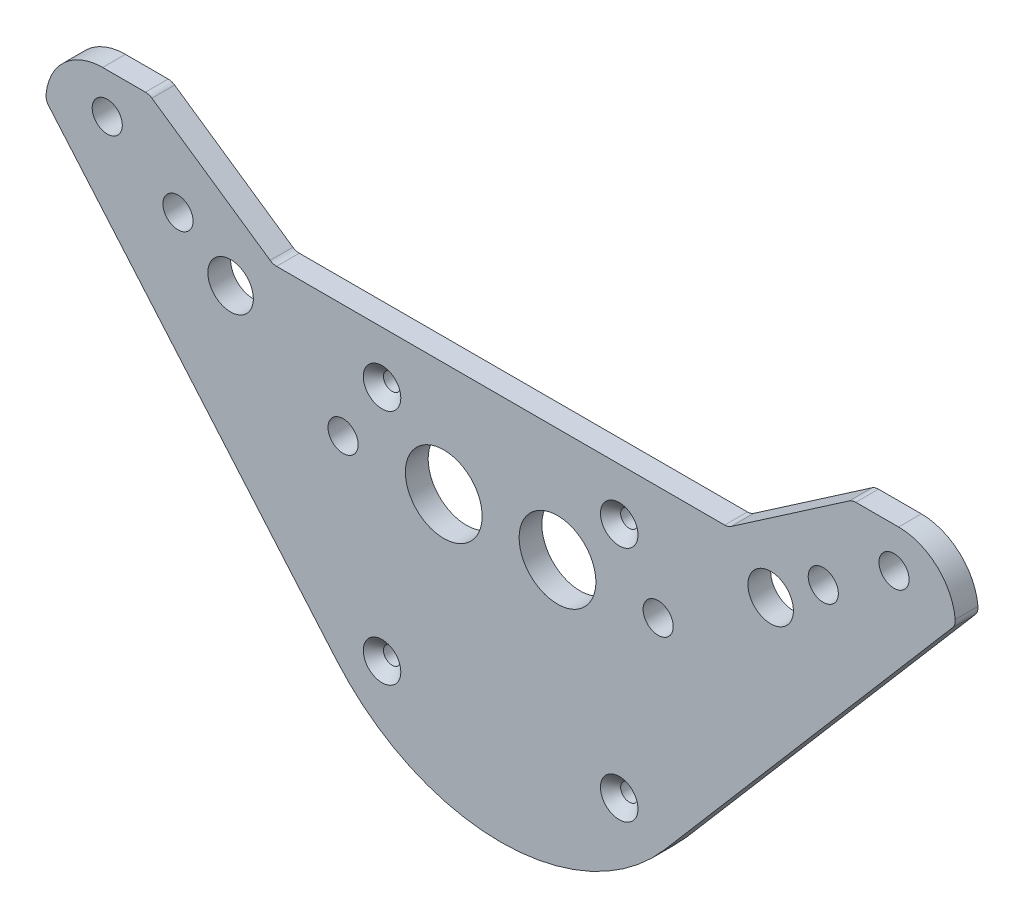
SolidWorks part; units mm, degrees
material "Thornel Mat VMA"
ref_plane "前视基准面" through (0, 0, 0) normal (0, 0, 1) x (1, 0, 0)
ref_plane "上视基准面" through (0, 0, 0) normal (0, 1, 0) x (1, 0, 0)
ref_plane "右视基准面" through (0, 0, 0) normal (1, 0, 0) x (0, 0, -1)
other "Configuration Table"
sketch "草图1" plane through (0, 0, 0) normal (0, 0, 1) x (1, 0, 0)
  line L1 (-80, -60) -> (80, -60)
  line L2 (-80, -60) -> (-80, 60)
  line L3 (-80, 60) -> (80, 60)
  line L4 (80, -60) -> (80, 60)
  line L5 (-80, -60) -> (80, 60) construction
  line L6 (-80, 60) -> (80, -60) construction
  point P0 (0, 0)
  dimension "D1" = 160
  dimension "D2" = 120
extrude "凸台-拉伸1" add sketch "草图1" along normal blind 4
sketch "草图2" plane through (0, 0, 0) normal (0, 0, -1) x (-1, 0, 0)
  line L0 (0, 0) -> (0, 63.5818) construction
  circle A0 centre (-47.5, 38) radius 4 construction
  circle A1 centre (-56.7499, 44.5391) radius 2.65 construction
  circle A2 centre (-69.1949, 52.913) radius 2.65 construction
  circle A3 centre (-47.5, 38) radius 4
  circle A4 centre (-56.7499, 44.5391) radius 2.65
  circle A5 centre (-69.1949, 52.913) radius 2.65
  circle A6 centre (-27.7116, 25) radius 2.65 construction
  circle A7 centre (-27.7116, 25) radius 2.65
  arc A8 (-7.5078, 29.0437) -> (-12.4922, 20.9563) centre (-10, 25) ccw construction
  arc A9 (-7.5078, 29.0437) -> (-12.4922, 20.9563) centre (-10, 25) ccw construction
  circle A10 centre (-10, 25) radius 6.75
  dimension "D1" = 2
extrude "切除-拉伸1" cut sketch "草图2" against normal blind 24
mirror "镜向1" about plane through (0, 0, 0) normal (1, 0, 0) of "切除-拉伸1"
sketch "草图3" plane through (0, 0, 0) normal (0, 0, -1) x (-1, 0, 0)
  line L0 (-61.8516, 60) -> (-40.0302, 45)
  line L1 (-80, 60) -> (80, 60) construction
  line L2 (-40.0302, 45) -> (40.0302, 45)
  line L3 (-69.1949, 52.913) -> (-47.5, 38) construction
  line L4 (0, 45) -> (0, 0) construction
  line L5 (69.1949, 52.913) -> (47.5, 38) construction
  line L6 (61.8516, 60) -> (40.0302, 45)
  line L7 (-61.8516, 60) -> (61.8516, 60)
  circle A0 centre (-10, 25) radius 6.75 construction
  dimension "D1" = 10
  dimension "D2" = 20
extrude "切除-拉伸2" cut sketch "草图3" against normal blind 54
sketch "草图5" plane through (0, 0, 0) normal (0, 0, -1) x (-1, 0, 0)
  line L0 (0, 0) -> (0, 45) construction
  line L1 (-40.0302, 45) -> (40.0302, 45) construction
  circle A0 centre (-20.8597, -5.8597) radius 1.5 construction
  circle A1 centre (-20.8597, 35.8597) radius 1.5 construction
  circle A2 centre (-20.8597, -5.8597) radius 1.5 construction
  circle A3 centre (-20.8597, 35.8597) radius 1.5 construction
  circle A4 centre (-20.8597, 35.8597) radius 1.525
  circle A5 centre (-20.8597, -5.8597) radius 1.525
  circle A6 centre (20.8597, 35.8597) radius 1.5 construction
  circle A7 centre (20.8597, -5.8597) radius 1.5 construction
  circle A8 centre (20.8597, -5.8597) radius 1.525
  circle A9 centre (20.8597, 35.8597) radius 1.525
  dimension "D1" = 3.05
extrude "切除-拉伸3" cut sketch "草图5" against normal blind 54
sketch "草图6" plane through (0, 0, 0) normal (0, 0, -1) x (-1, 0, 0)
  line L0 (-80, 50) -> (-28.8634, -9.7164)
  line L1 (-80, -60) -> (-80, 60) construction
  line L2 (28.8634, -9.7164) -> (80, 50)
  line L3 (80, 60) -> (80, -60) construction
  line L4 (61.8516, 60) -> (80, 60) construction
  line L5 (-80, 60) -> (-61.8516, 60) construction
  line L6 (-80, 50) -> (-80, -60)
  line L7 (-80, -60) -> (80, -60)
  line L8 (80, -60) -> (80, 50)
  circle A1 centre (0, 15) radius 38
  arc A2 (-28.8634, -9.7164) -> (28.8634, -9.7164) centre (0, 15) ccw
  dimension "D2" = 10
  dimension "D3" = 10
  dimension "D1" = 0
extrude "切除-拉伸4" cut sketch "草图6" against normal blind 84
fillet "圆角1" radius 10 2 edges at (-80, 60, 2) (80, 60, 2)
hole_wizard "M3 十字槽半沉头木螺钉的锥形沉头孔1" positions "草图7" profile "草图8" countersink size "M3" standard "GB"
sketch "草图7" plane through (0, 0, 4) normal (0, 0, 1) x (1, 0, 0)
  point P0 (-20.8597, 35.8597)
  point P3 (20.8597, 35.8597)
  point P6 (20.8597, -5.8597)
  point P9 (-20.8597, -5.8597)
sketch "草图8" plane through (-20.8597, 35.8597, 4) normal (1, 0, 0) x (0, -1, 0)
  line L0 (0, 0) -> (0, 8.4163)
  line L1 (0, 8.4163) -> (1.525, 7.5)
  line L2 (1.525, 7.5) -> (1.525, 1.775)
  line L3 (1.525, 1.775) -> (3.3, 0)
  line L5 (3.3, 0) -> (0, 0)
  line L6 (-1.525, 1.775) -> (-3.3, 0) construction
  line L10 (0, 8.4163) -> (-1.525, 7.5) construction
  line L11 (0, -6.35) -> (0, 107.95) construction
  dimension "孔直径" = 3.05
  dimension "孔深度" = 7.5
  dimension "近端锥形沉头孔直径" = 6.6
  dimension "近端锥形沉头孔角度" = 90
  dimension "导头角度" = 118
fillet "圆角2" radius 2 6 edges at (-61.8516, 60, 2) (-40.0302, 45, 2) (80, 50, 2) (-80, 50, 2) (40.0302, 45, 2) (61.8516, 60, 2)
